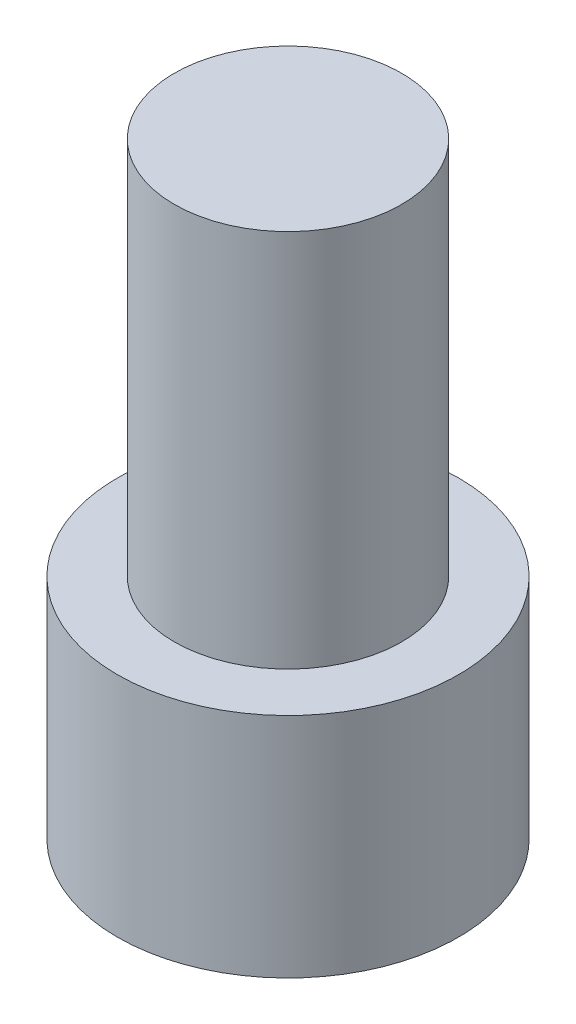
SolidWorks part; units mm, degrees
ref_plane "Front Plane" through (0, 0, 0) normal (0, 0, 1) x (1, 0, 0)
ref_plane "Top Plane" through (0, 0, 0) normal (0, 1, 0) x (1, 0, 0)
ref_plane "Right Plane" through (0, 0, 0) normal (1, 0, 0) x (0, 0, -1)
sketch "Sketch1" plane through (0, 0, 0) normal (0, 1, 0) x (1, 0, 0)
  circle A0 centre (0, 0) radius 6
  circle A1 centre (0, 0) radius 9
  dimension "D1" = 18
  dimension "D2" = 12
extrude "Boss-Extrude1" add sketch "Sketch1" along normal blind 12 contours A1
extrude "Boss-Extrude2" add sketch "Sketch1<3>" along normal blind 32 contours A0
sketch "Sketch1<3>" plane through (0, 0, 0) normal (0, 1, 0) x (1, 0, 0) same geometry as "Sketch1"
cosmetic thread "Cosmetic Thread1" parameters "D2"=10.072
sketch "Sketch2" plane through (0, 0, 0) normal (0, -1, 0) x (1, 0, 0)
  line L1 (-3.5, -6.0622) -> (3.5, -6.0622)
  line L2 (3.5, -6.0622) -> (7, 0)
  line L3 (7, 0) -> (3.5, 6.0622)
  line L4 (3.5, 6.0622) -> (-3.5, 6.0622)
  line L5 (-3.5, 6.0622) -> (-7, 0)
  line L6 (-7, 0) -> (-3.5, -6.0622)
  circle A0 centre (0, 0) radius 6.0622 construction
  dimension "D1" = 14
extrude "Cut-Extrude1" cut sketch "Sketch2" against normal blind 6
